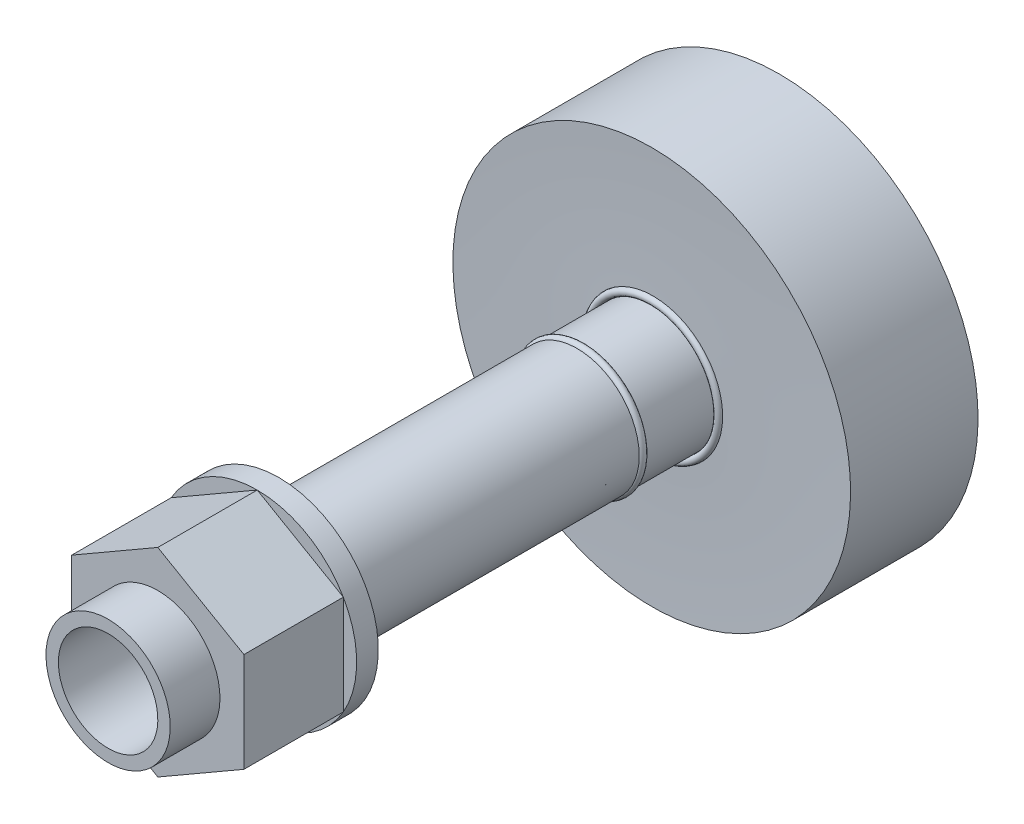
SolidWorks part; units mm, degrees
ref_plane "Front Plane" through (0, 0, 0) normal (0, 0, 1) x (1, 0, 0)
ref_plane "Top Plane" through (0, 0, 0) normal (0, 1, 0) x (1, 0, 0)
ref_plane "Right Plane" through (0, 0, 0) normal (1, 0, 0) x (0, 0, -1)
sketch "Sketch1" plane through (0, 0, 0) normal (1, 0, 0) x (0, 0, -1)
  line L0 (123.2538, 0) -> (-250, 0) construction
  line L1 (-126.7462, 20) -> (-126.7462, 40)
  line L2 (-126.7462, 40) -> (-78.0303, 40)
  line L4 (-76.7462, 25) -> (73.2538, 25)
  line L5 (123.2538, 20) -> (-126.7462, 20)
  line L6 (123.2538, 0.7576) -> (123.2538, 0)
  line L8 (123.2538, 80) -> (123.2538, 20)
  line L9 (123.2538, 0) -> (123.2538, 0.7576)
  line L11 (71.9697, 80) -> (123.2538, 80)
  line L13 (73.2538, 25) -> (72.4575, 25)
  line L14 (-126.7462, 25) -> (-146.7462, 25)
  line L15 (-146.7462, 25) -> (-146.7462, 20)
  line L16 (-146.7462, 20) -> (-126.7462, 20)
  arc A0 (-76.7462, 25) -> (-78.0303, 40) centre (-924.2572, -40) ccw
  arc A2 (72.4575, 25) -> (71.9697, 80) centre (-927.3689, 43.6351) ccw
  dimension "D7" = 1700
  dimension "D2" = 25
  dimension "D3" = 80
  dimension "D4" = 40
  dimension "D5" = 20
  dimension "D1" = 50
  dimension "D6" = 50
  dimension "D8" = 20
  dimension "D9" = 150
revolve "Revolve1" add sketch "Sketch1" angle 360 about L0 region at (0, 22.5, 136.7462) region at (0, 22.5, 124.1752)
sketch "Sketch2" plane through (0, 0, 126.7462) normal (0, 0, 1) x (1, 0, 0)
  line L0 (0, 0) -> (38.5975, 0) construction
  line L1 (34.641, -20) -> (34.641, 20)
  line L2 (34.641, 20) -> (0, 40)
  line L3 (0, 40) -> (-34.641, 20)
  line L4 (-34.641, 20) -> (-34.641, -20)
  line L5 (-34.641, -20) -> (0, -40)
  line L6 (0, -40) -> (34.641, -20)
  line L7 (0, 0) -> (34.641, 20) construction
  circle A0 centre (0, 0) radius 34.641 construction
  circle A1 centre (0, 0) radius 47.4757
  dimension "D1" = 30
extrude "Cut-Extrude1" cut sketch "Sketch2" against normal blind 40
sketch "Sketch3" plane through (0, 0, 0) normal (0, 1, 0) x (1, 0, 0)
  line L0 (80, 71.9697) -> (-80, 71.9697) construction
  line L1 (25, 71.9697) -> (28, 71.9697)
  line L2 (25, 71.9697) -> (25, 73.9697)
  line L3 (25, 73.9697) -> (28, 73.9697)
  line L4 (28, 71.9697) -> (28, 73.9697)
  line L5 (25, -76.7462) -> (25, 72.4575) construction
  line L6 (0, 0) -> (0, 145.935) construction
  line L8 (25, 44.9306) -> (23, 44.9306)
  line L9 (25, 44.9306) -> (25, 41.9306)
  line L10 (25, 41.9306) -> (23, 41.9306)
  line L11 (23, 44.9306) -> (23, 41.9306)
  line L12 (25, -76.7462) -> (28, -76.7462)
  line L13 (25, -76.7462) -> (25, -78.7462)
  line L14 (25, -78.7462) -> (28, -78.7462)
  line L15 (28, -76.7462) -> (28, -78.7462)
  dimension "D1" = 2
  dimension "D2" = 3
  dimension "D3" = 2
  dimension "D4" = 3
  dimension "D5" = 2
  dimension "D6" = 3
revolve "Cut-Revolve1" cut sketch "Sketch3" angle 360 about L6
sketch "Sketch4" plane through (0, 0, 0) normal (0, 1, 0) x (1, 0, 0)
  line L0 (0, 154.6414) -> (0, -221.434) construction
  line L2 (19.9988, -90.7059) -> (21.9988, -90.7059)
  line L3 (19.9988, -90.7059) -> (19.9988, -93.7059)
  line L4 (19.9988, -93.7059) -> (21.9988, -93.7059)
  line L5 (21.9988, -90.7059) -> (21.9988, -93.7059)
  line L6 (19.9988, 87.725) -> (21.9988, 87.725)
  line L7 (19.9988, 87.725) -> (19.9988, 84.725)
  line L8 (19.9988, 84.725) -> (21.9988, 84.725)
  line L9 (21.9988, 87.725) -> (21.9988, 84.725)
  dimension "D1" = 2
  dimension "D2" = 3
  dimension "D3" = 2
  dimension "D4" = 3
revolve "Cut-Revolve2" cut sketch "Sketch4" angle 360 about L0
sketch "Sketch5" plane through (0, 0, 0) normal (0, 1, 0) x (1, 0, 0)
  line L0 (-28, 72.5089) -> (28, 72.5089) construction
  line L2 (0, 162.7228) -> (0, -163.8507) construction
  circle A0 centre (24.5, 43.4306) radius 1.5
  circle A1 centre (26.5032, 72.5089) radius 1.4649
  circle A2 centre (20.4923, 86.2421) radius 1.4
  circle A3 centre (26.5032, -77.2648) radius 1.4388
  circle A4 centre (20.4923, -92.2495) radius 1.4
  dimension "D1" = 2.8
  dimension "D2" = 2.8
revolve "Revolve2" add sketch "Sketch5" angle 360 about L2
equation "\"mountAngle\" = 30deg"
equation "\"ThrusterDim\"= 140mm"
equation "\"hatchHoleDiameter\"= 600mm"
equation "\"hullThickness\"= 150mm"
equation "\"gasketHullInterconnectWidth\"= 100mm"
equation "\"collarThickness\"= 15"
equation "\"hatchTunnelLength\"=200"
equation "\"oRingDiameter\"=2"
equation "\"boltPatternRadiusInterconnect\"=500"
equation "\"interconnectBoltDiameter\"=30"
equation "\"hatchShaftDiameter\"=20"
equation "\"hatchMinima\"=50"
equation "\"hullDiameter\"=2000"
equation "\"hatchMaxima\"=180"
equation "\"bushingFlatHatch\"=15"
equation "\"hingePivotDiameter\"=20"
equation "\"handleWidth\"=250"
equation "\"handleHeight\"=160"
equation "\"handleThickness\"=25"
equation "\"FrameLength\"= 4300"
equation "\"FrameMidLength\"= 3000"
equation "\"TubeOD\"= 100"
equation "\"FrameBackFlat\"= 800"
equation "\"TubeWall\"=15"
equation "\"TopMemberAngle\"=120"
equation "\"FrameHight\"= 2500"
equation "\"D7@Sketch1\"=\"hullDiameter\" - \"hullThickness\" *2"
equation "\"D9@Sketch1\"=\"hullThickness\""
